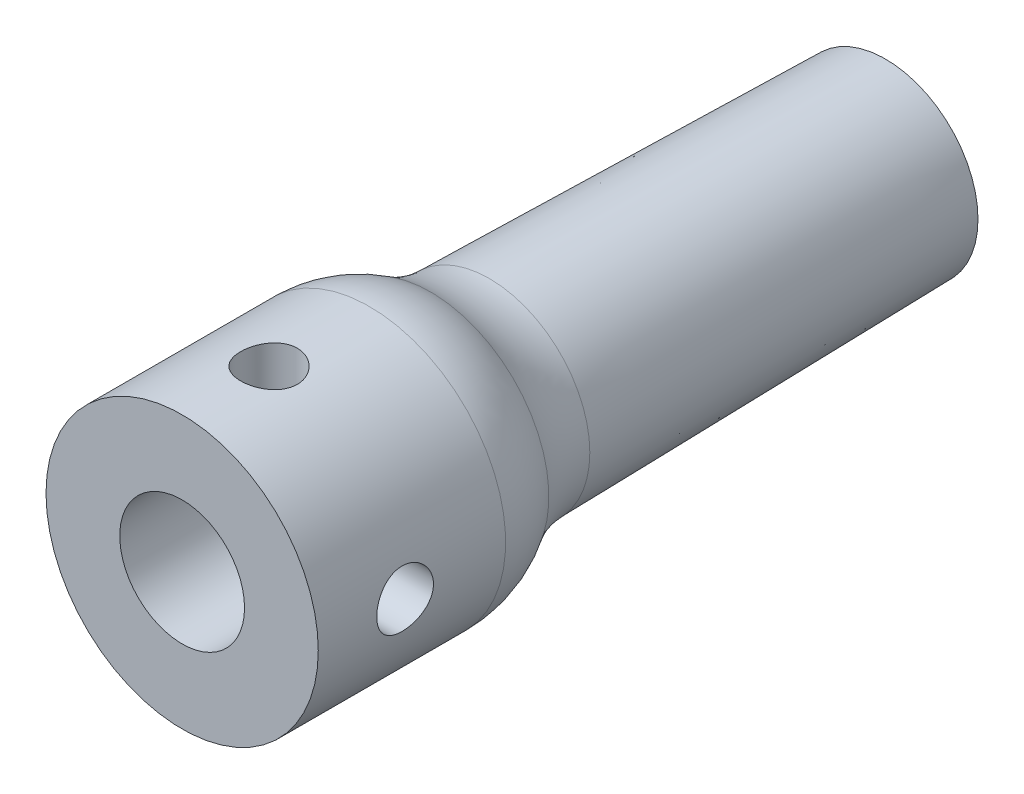
SolidWorks part; units mm, degrees
ref_plane "Front" through (0, 0, 0) normal (0, 0, 1) x (1, 0, 0)
ref_plane "Top" through (0, 0, 0) normal (0, 1, 0) x (1, 0, 0)
ref_plane "Right" through (0, 0, 0) normal (1, 0, 0) x (0, 0, -1)
sketch "Sketch1" plane through (0, 0, 0) normal (0, 0, 1) x (1, 0, 0)
  circle A0 centre (0, 0) radius 2.75
  circle A1 centre (0, 0) radius 4.5
  dimension "D1" = 5.5
  dimension "D2" = 9
extrude "Boss-Extrude1" add sketch "Sketch1" along normal blind 21
draft "Draft1" type of draft neutral plane draft angle 1.16 faces to draft 1 face at (4.5, 0, 21) neutral plane through (0, 0, 21) neutral plane normal (0, 0, 1) reverse direction yes parameters "D1"=1.16
sketch "Sketch2" plane through (0, 0, 21) normal (0, 0, 1) x (1, 0, 0)
  circle A0 centre (0, 0) radius 6
  circle A1 centre (0, 0) radius 2.75
  dimension "D1" = 12
extrude "Boss-Extrude2" add sketch "Sketch2" along normal blind 10
fillet "Fillet1" radius 5 1 edges at (4.5, 0, 21)
fillet "Fillet2" radius 5 1 edges at (6, 0, 21)
sketch "Sketch3" plane through (0, 0, 31) normal (0, 0, 1) x (1, 0, 0)
  circle A0 centre (0, 0) radius 6 construction
  point P0 (6, 0)
ref_plane "Plane1" through (6, 0, 31) normal (1, 0, 0) x (0, 0, -1)
sketch "Sketch4" plane through (6, 0, 31) normal (1, 0, 0) x (0, 0, -1)
  line L0 (0, -6) -> (8.2572, -6) construction
  circle A0 centre (3.827, 0) radius 1.25
  dimension "D2" = 2.5
  dimension "D1" = 6
extrude "Cut-Extrude1" cut sketch "Sketch4" against normal up to next
pattern_circular "CirPattern1" count 2 every 90 about axis through (0, 0, 31) along (0, 0, 1) of "Cut-Extrude1"
